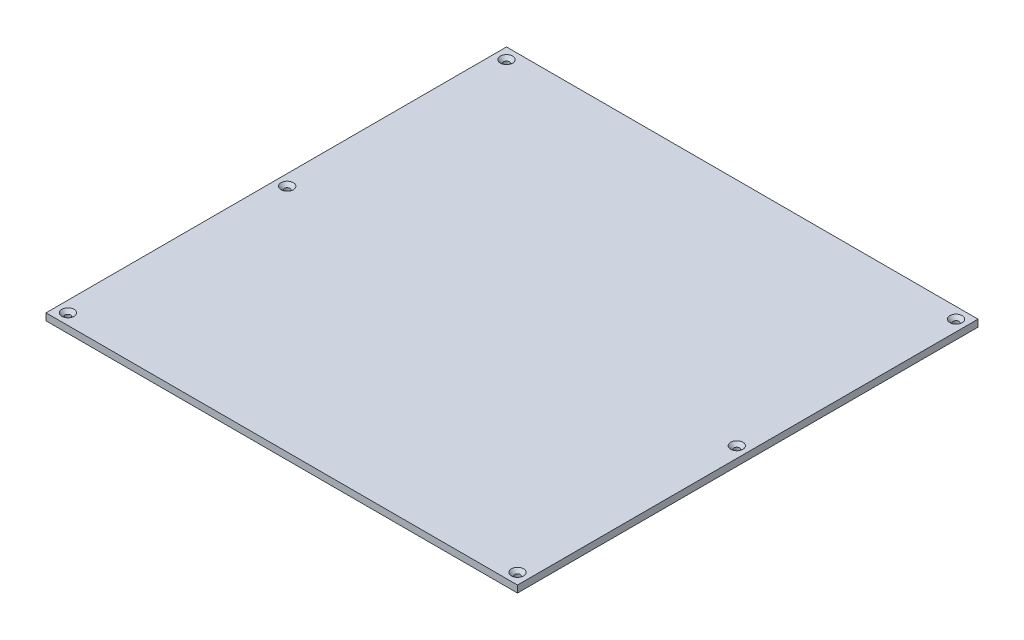
SolidWorks part; units mm, degrees
material "6063-T5"
ref_plane "Front Plane" through (0, 0, 0) normal (0, 0, 1) x (1, 0, 0)
ref_plane "Top Plane" through (0, 0, 0) normal (0, 1, 0) x (1, 0, 0)
ref_plane "Right Plane" through (0, 0, 0) normal (1, 0, 0) x (0, 0, -1)
sketch "Sketch2" plane through (0, 0, 0) normal (0, 1, 0) x (1, 0, 0)
  line L0 (-215, -210) -> (215, -210)
  line L1 (-215, -210) -> (-215, 210)
  line L2 (215, -210) -> (215, 210)
  line L3 (-215, 210) -> (215, 210)
  line L4 (-215, -210) -> (215, 210) construction
  line L5 (215, -210) -> (-215, 210) construction
  line L6 (-205, 200) -> (205, 200) construction
  line L7 (205, 200) -> (205, -200) construction
  line L8 (205, -200) -> (-205, -200) construction
  line L9 (-205, -200) -> (-205, 200) construction
  line L10 (0, 301.643) -> (0, -298.9072) construction
  line L11 (-264.2047, 0) -> (279.6955, 0) construction
  circle A0 centre (-205, 200) radius 2.6
  circle A1 centre (205, 200) radius 2.6
  circle A2 centre (205, -200) radius 2.6
  circle A3 centre (-205, -200) radius 2.6
  circle A4 centre (-205, 0) radius 2.6
  circle A5 centre (205, 0) radius 2.6
  point P1 (0, 0)
  point P14 (0, 200)
  point P15 (205, 0)
  dimension "D3" = 5.2
  dimension "D1" = 430
  dimension "D2" = 420
  dimension "D4" = 410
  dimension "D5" = 400
extrude "Boss-Extrude1" add sketch "Sketch2" along normal mid plane 6.35
ref_axis "Axis1" through (-205, 3.175, -200) along (0, -1, 0)
ref_axis "Axis3" through (-205, 3.175, 200) along (0, -1, 0)
ref_axis "Axis4" through (205, 3.175, 0) along (0, -1, 0)
chamfer "Chamfer1" distance 3 angle 45 6 edges at (-205, 3.175, 2.6) (205, 3.175, 2.6) (205, 3.175, -197.4) (205, 3.175, 202.6) (-205, 3.175, 202.6) (-205, 3.175, -197.4)
